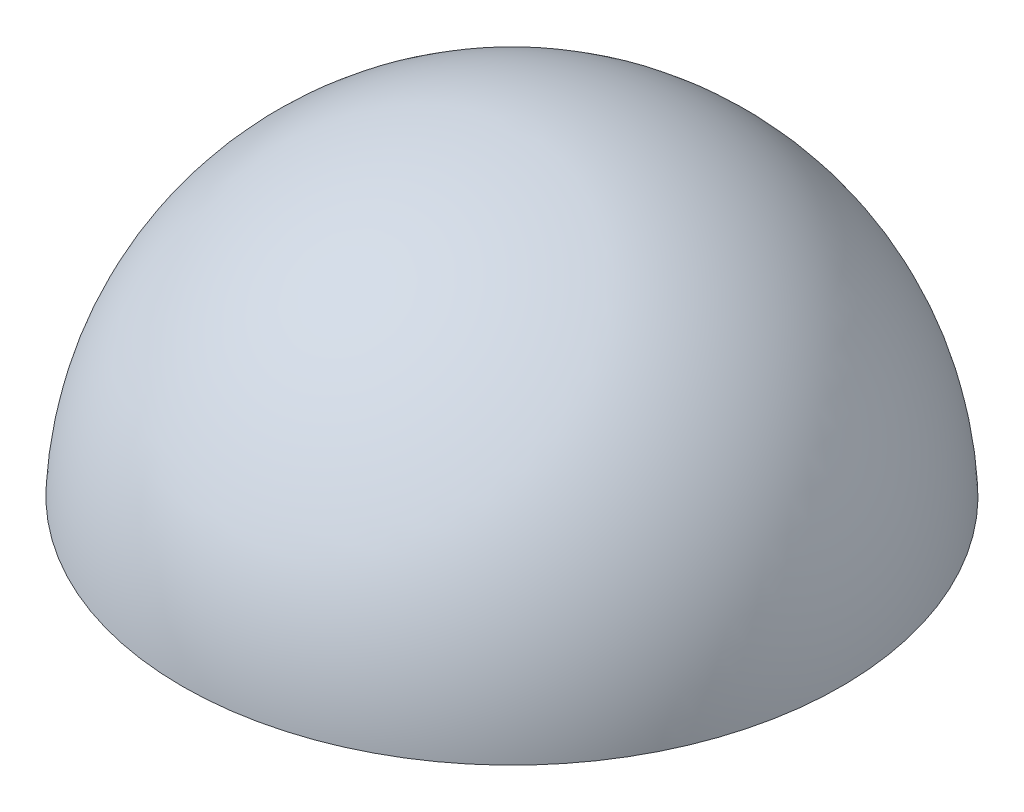
SolidWorks part; units mm, degrees
ref_plane "Front Plane" through (0, 0, 0) normal (0, 0, 1) x (1, 0, 0)
ref_plane "Top Plane" through (0, 0, 0) normal (0, 1, 0) x (1, 0, 0)
ref_plane "Right Plane" through (0, 0, 0) normal (1, 0, 0) x (0, 0, -1)
sketch "Sketch1" plane through (0, 0, 0) normal (0, 1, 0) x (1, 0, 0)
  line L0 (0, -44.45) -> (0, 44.45)
  arc A0 (0, 44.45) -> (0, -44.45) centre (0, 0) ccw
  arc A1 (0, 42.45) -> (0, -42.45) centre (0, 0) ccw
  circle A3 centre (0, 0) radius 44.45 construction
  circle A4 centre (0, 0) radius 42.45 construction
  point P1 (42.45, 0)
  point P6 (42.5077, 12.9959)
  dimension "D1" = 88.9
  dimension "D2" = 2
revolve "Revolve1" add sketch "Sketch1" angle 180 about L0 region at (-43.4561, 0, 0)
sketch "Sketch2" plane through (0, 0, 0) normal (0, 1, 0) x (1, 0, 0)
  circle A0 centre (0, 0) radius 44.45
extrude "Cut-Extrude1" cut sketch "Sketch2" along normal blind 2
sketch "30deg" plane through (0, 0, 0) normal (1, 0, 0) x (0, 0, -1)
  line L0 (-1000, 0) -> (49000, 0) construction
  line L1 (0, 0) -> (43.45, 0)
  line L2 (44.45, 0.5) -> (43.45, 0.5)
  line L3 (43.45, 0.5) -> (43.45, -0.5)
  line L4 (43.45, -0.5) -> (44.45, -0.5)
  line L5 (44.45, 0.5) -> (44.45, -0.5)
  line L6 (38.2448, 22.658) -> (37.3788, 22.158)
  line L7 (0, 0) -> (-44.45, 0)
  line L8 (0, 0) -> (44.45, 0) construction
  line L9 (37.3788, 22.158) -> (37.8788, 21.292)
  line L10 (0, 0) -> (-38.4948, 22.225)
  line L11 (0, 0) -> (-22.225, 38.4948)
  line L12 (0, 0) -> (38.4948, 22.225)
  line L13 (0, 0) -> (22.225, 38.4948)
  line L14 (0, 0) -> (0, 44.45)
  line L15 (37.8788, 21.292) -> (38.7448, 21.792)
  line L16 (38.2448, 22.658) -> (38.7448, 21.792)
  line L17 (0, 0) -> (37.6288, 21.725)
  line L18 (21.792, 38.7448) -> (21.292, 37.8788)
  line L19 (21.292, 37.8788) -> (22.158, 37.3788)
  line L20 (22.158, 37.3788) -> (22.658, 38.2448)
  line L21 (21.792, 38.7448) -> (22.658, 38.2448)
  line L22 (0, 0) -> (21.725, 37.6288)
  line L23 (0, 0) -> (43.45, 0) construction
  line L24 (0, 0) -> (37.6288, 21.725) construction
  line L25 (0, -1000) -> (0, 49000) construction
  arc A1 (44.405, 2) -> (-44.405, 2) centre (0, 0) ccw construction
  point P14 (44.45, 0)
  point P29 (38.4948, 22.225)
  point P35 (22.225, 38.4948)
  dimension "D2" = 1
  dimension "D3" = 1
  dimension "D5" = 30
  dimension "D1" = 7
  dimension "D4" = 3
sketch "Sketch4" plane through (0, 0, 0) normal (0, 1, 0) x (1, 0, 0)
  line L0 (0, 0) -> (0, 43.45)
  line L1 (0.5, 44.45) -> (-0.5, 44.45)
  line L2 (-0.5, 43.45) -> (0.5, 43.45)
  line L3 (-0.5, 43.45) -> (-0.5, 44.45)
  line L4 (0.5, 43.45) -> (0.5, 44.45)
  line L5 (0, 0) -> (21.725, 37.6288)
  line L6 (21.292, 37.8788) -> (21.792, 38.7448)
  line L7 (21.292, 37.8788) -> (22.158, 37.3788)
  line L8 (22.158, 37.3788) -> (22.658, 38.2448)
  line L9 (22.658, 38.2448) -> (21.792, 38.7448)
  line L10 (0, 0) -> (37.6288, 21.725)
  line L11 (37.3788, 22.158) -> (38.2448, 22.658)
  line L12 (37.3788, 22.158) -> (37.8788, 21.292)
  line L13 (37.8788, 21.292) -> (38.7448, 21.792)
  line L14 (38.7448, 21.792) -> (38.2448, 22.658)
  line L15 (0, 0) -> (43.45, 0)
  line L16 (43.45, 0.5) -> (44.45, 0.5)
  line L17 (43.45, 0.5) -> (43.45, -0.5)
  line L18 (43.45, -0.5) -> (44.45, -0.5)
  line L19 (44.45, -0.5) -> (44.45, 0.5)
  line L20 (0, 0) -> (37.6288, -21.725)
  line L21 (37.8788, -21.292) -> (38.7448, -21.792)
  line L22 (37.8788, -21.292) -> (37.3788, -22.158)
  line L23 (37.3788, -22.158) -> (38.2448, -22.658)
  line L24 (38.2448, -22.658) -> (38.7448, -21.792)
  line L25 (0, 0) -> (21.725, -37.6288)
  line L26 (22.158, -37.3788) -> (22.658, -38.2448)
  line L27 (22.158, -37.3788) -> (21.292, -37.8788)
  line L28 (21.292, -37.8788) -> (21.792, -38.7448)
  line L29 (21.792, -38.7448) -> (22.658, -38.2448)
  line L30 (0, 0) -> (0, -43.45)
  line L31 (0.5, -43.45) -> (0.5, -44.45)
  line L32 (0.5, -43.45) -> (-0.5, -43.45)
  line L33 (-0.5, -43.45) -> (-0.5, -44.45)
  line L34 (-0.5, -44.45) -> (0.5, -44.45)
  line L35 (0, 0) -> (-21.725, -37.6288)
  line L36 (-21.292, -37.8788) -> (-21.792, -38.7448)
  line L37 (-21.292, -37.8788) -> (-22.158, -37.3788)
  line L38 (-22.158, -37.3788) -> (-22.658, -38.2448)
  line L39 (-22.658, -38.2448) -> (-21.792, -38.7448)
  line L40 (0, 0) -> (-37.6288, -21.725)
  line L41 (-37.3788, -22.158) -> (-38.2448, -22.658)
  line L42 (-37.3788, -22.158) -> (-37.8788, -21.292)
  line L43 (-37.8788, -21.292) -> (-38.7448, -21.792)
  line L44 (-38.7448, -21.792) -> (-38.2448, -22.658)
  line L45 (0, 0) -> (-43.45, 0)
  line L46 (-43.45, -0.5) -> (-44.45, -0.5)
  line L47 (-43.45, -0.5) -> (-43.45, 0.5)
  line L48 (-43.45, 0.5) -> (-44.45, 0.5)
  line L49 (-44.45, 0.5) -> (-44.45, -0.5)
  line L50 (0, 0) -> (-37.6288, 21.725)
  line L51 (-37.8788, 21.292) -> (-38.7448, 21.792)
  line L52 (-37.8788, 21.292) -> (-37.3788, 22.158)
  line L53 (-37.3788, 22.158) -> (-38.2448, 22.658)
  line L54 (-38.2448, 22.658) -> (-38.7448, 21.792)
  line L55 (0, 0) -> (-21.725, 37.6288)
  line L56 (-22.158, 37.3788) -> (-22.658, 38.2448)
  line L57 (-22.158, 37.3788) -> (-21.292, 37.8788)
  line L58 (-21.292, 37.8788) -> (-21.792, 38.7448)
  line L59 (-21.792, 38.7448) -> (-22.658, 38.2448)
  line L60 (0, 0) -> (0, 43.45) construction
  line L61 (0, 0) -> (21.725, 37.6288) construction
  circle A0 centre (0, 0) radius 44.45 construction
  point P7 (0, 44.45)
  point P10 (0, 43.45)
  dimension "D1" = 88.9
  dimension "D2" = 1
  dimension "D3" = 1
  dimension "D5" = 30
  dimension "D4" = 12
ref_plane "Plane1" through (0, 44.45, 0) normal (0, 1, 0) x (1, 0, 0)
sketch "Sketch5" plane through (0, 44.45, 0) normal (0, 1, 0) x (1, 0, 0)
  circle A0 centre (0, 0) radius 0.5
  dimension "D1" = 1
sketch "Sketch6" plane through (0, 0, 0) normal (0, 0, 1) x (1, 0, 0)
  line L0 (44.45, 0) -> (-44.45, 0) construction
  line L1 (-43.45, 0) -> (-44.45, 0) construction
  arc A0 (-44.45, 0) -> (0, 44.45) centre (0, 0) cw
ref_axis "Axis1" through (0, 117.8347, 0) along (0, -1, 0)
